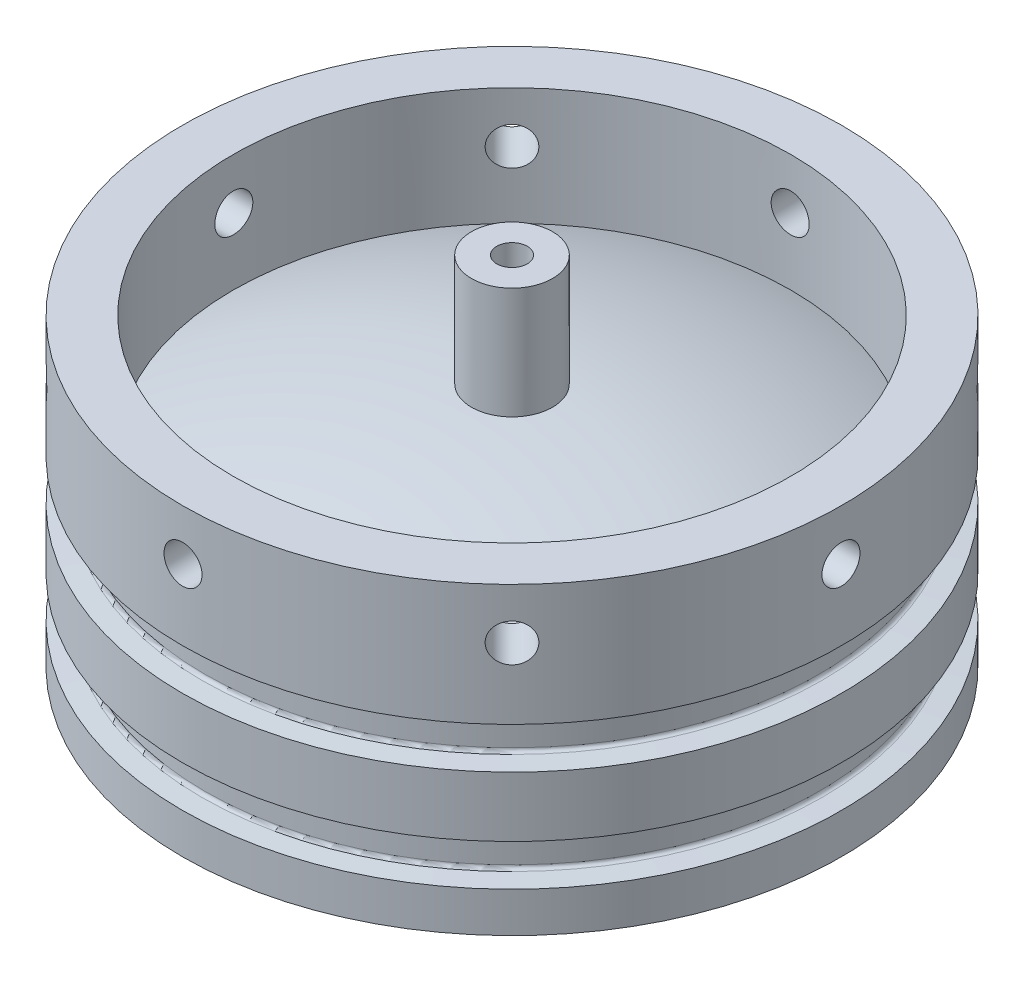
SolidWorks part; units mm, degrees
material "6061-T6 (SS)"
ref_plane "Front Plane" through (0, 0, 0) normal (0, 0, 1) x (1, 0, 0)
ref_plane "Top Plane" through (0, 0, 0) normal (0, 1, 0) x (1, 0, 0)
ref_plane "Right Plane" through (0, 0, 0) normal (1, 0, 0) x (0, 0, -1)
ref_axis "Axis1" through (0, -55, 0) along (0, 1, 0)
sketch "Sketch1" plane through (0, 0, 0) normal (0, 0, 1) x (1, 0, 0)
  line L3 (0, -55) -> (0, 55) construction
  line L4 (-41.275, 0) -> (-41.275, 38.1)
  line L5 (-41.275, 38.1) -> (-34.925, 38.1)
  line L6 (-34.925, 38.1) -> (-34.925, 23.3872)
  line L8 (-5.08, 44.6435) -> (-5.08, 30.6735)
  line L9 (-5.08, 44.6435) -> (-1.9133, 44.6435)
  line L10 (-1.9133, 44.6435) -> (-1.9133, 21.2751)
  line L11 (-41.275, 0) -> (-34.925, 0)
  line L12 (55, 0) -> (-55, 0) construction
  arc A0 (-34.925, 0) -> (-21.1667, 18.3003) centre (-15.875, 0) cw
  arc A1 (-21.1667, 18.3003) -> (-1.9133, 21.2751) centre (0, -54.9009) cw
  arc A2 (-5.08, 30.6735) -> (-34.925, 23.3872) centre (0, -54.9009) ccw
  point P0 (-36.6847, 19.05)
  point P2 (-35.8893, 15.6209)
  dimension "D4" = 19.05
  dimension "D5" = 76.2
  dimension "D8" = 85.725
  dimension "D2" = 6.35
  dimension "D3" = 41.275
  dimension "D6" = 6.35
  dimension "D9" = 5.08
  dimension "D10" = 1.9133
  dimension "D11" = 38.1
  dimension "D12" = 13.97
revolve "Revolve1" add sketch "Sketch1" angle 360 about axis through (0, -55, 0) along (0, 1, 0)
ref_plane "Plane1" through (0, -55, 0) normal (-1, 0, 0) x (0, 0, -1)
sketch "Sketch3" plane through (0, -55, 0) normal (-1, 0, 0) x (0, 0, -1)
  line L0 (38.8614, -60.2451) -> (41.3639, -60.0262)
  line L1 (41.3639, -60.0262) -> (41.3639, -65.2138)
  line L2 (41.3639, -65.2138) -> (38.8614, -64.9949)
  line L3 (38.4556, -64.5521) -> (38.4556, -60.6879)
  line L4 (0, 50) -> (0, -50) construction
  line L5 (41.275, -55) -> (-41.275, -55) construction
  arc A0 (38.8614, -64.9949) -> (38.4556, -64.5521) centre (38.9001, -64.5521) cw
  arc A1 (38.4556, -60.6879) -> (38.8614, -60.2451) centre (38.9001, -60.6879) cw
  point P11 (41.3639, -62.62)
  dimension "D5" = 0.4445
  dimension "D6" = 0.4445
  dimension "D1" = 5.1877
  dimension "D2" = 2.5025
  dimension "D3" = 2.5025
  dimension "D4" = 3.8642
  dimension "D7" = 85
  dimension "D8" = 85
  dimension "D9" = 7.62
revolve "Groove for AS 568-234, O-Ring1" cut sketch "Sketch3"
pattern_linear "LPattern1" count 2 spacing 12.7 along (0, 1, 0) of "Groove for AS 568-234, O-Ring1"
ref_plane "Plane2" through (0, 31.75, 0) normal (0, 1, 0) x (1, 0, 0)
ref_axis "Axis2" through (0, 31.75, 45.4025) along (0, 0, -1)
hole_wizard "3/16 (0.1875) Diameter Hole1" positions "3DSketch1" profile "Sketch4" hole size "3/16" standard "ANSI Inch" end condition up to next
sketch3d "3DSketch1"
  line L0 (0, 31.75, 45.4025) -> (0, 31.75, -45.4025) construction
  point P0 (0, 31.75, 41.275)
  point P3 (0, 0, 0)
sketch "Sketch4" plane through (0, 31.75, 41.275) normal (1, 0, 0) x (0, -1, 0)
  line L0 (0, 0) -> (0, 6.35)
  line L1 (0, 6.35) -> (2.3812, 6.35)
  line L2 (2.3812, 6.35) -> (2.3812, 0)
  line L5 (2.3812, 0) -> (0, 0)
  line L11 (0, -6.35) -> (0, 107.95) construction
  dimension "Thru Hole Dia." = 4.7625
  dimension "Thru Hole Depth" = 6.35
pattern_circular "CirPattern1" count 8 over 360 about axis through (0, -55, 0) along (0, 1, 0) of "3/16 (0.1875) Diameter Hole1" reverse direction yes
